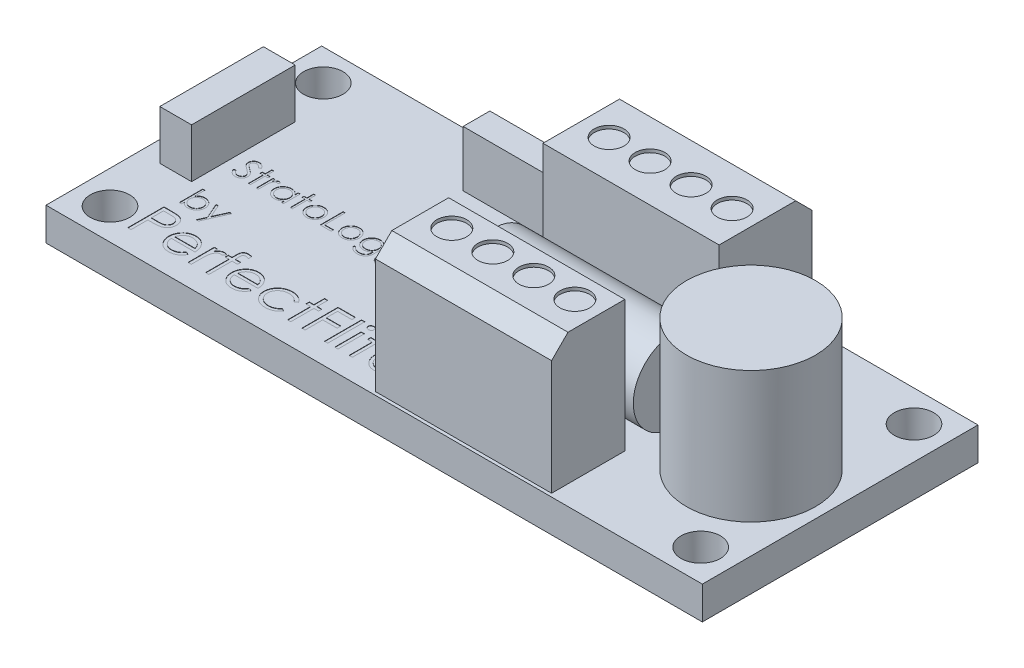
SolidWorks part; units mm, degrees
ref_plane "Front Plane" through (0, 0, 0) normal (0, 0, 1) x (1, 0, 0)
ref_plane "Top Plane" through (0, 0, 0) normal (0, 1, 0) x (1, 0, 0)
ref_plane "Right Plane" through (0, 0, 0) normal (1, 0, 0) x (0, 0, -1)
sketch "Sketch1" plane through (0, 0, 0) normal (0, 1, 0) x (1, 0, 0)
  line L1 (-19.9595, 12.6467) -> (30.8405, 12.6467)
  line L2 (-19.9595, 12.6467) -> (-19.9595, -8.6893)
  line L3 (-19.9595, -8.6893) -> (30.8405, -8.6893)
  line L4 (30.8405, 12.6467) -> (30.8405, -8.6893)
  dimension "D1" = 21.336
  dimension "D2" = 50.8
extrude "Boss-Extrude1" add sketch "Sketch1" along normal blind 1.27
sketch "Sketch2" plane through (0, 1.27, 0) normal (0, 1, 0) x (1, 0, 0)
  line L0 (-19.9595, 12.6467) -> (-19.9595, -8.6893) construction
  line L1 (30.8405, -8.6893) -> (30.8405, 12.6467) construction
  line L2 (-19.9595, -8.6893) -> (30.8405, -8.6893) construction
  circle A0 centre (-17.4195, 10.2337) radius 1.524
  circle A1 centre (28.3005, 10.2337) radius 1.524
  circle A2 centre (28.3005, -6.2763) radius 1.524
  circle A3 centre (-17.4195, -6.2763) radius 1.524
  dimension "D1" = 3.048
  dimension "D2" = 3.048
  dimension "D3" = 3.048
  dimension "D4" = 3.048
  dimension "D5" = 45.72
  dimension "D6" = 45.72
  dimension "D7" = 16.51
  dimension "D8" = 16.51
  dimension "D9" = 2.54
  dimension "D10" = 2.54
  dimension "D11" = 2.413
extrude "Cut-Extrude1" cut sketch "Sketch2" against normal blind 1.27
sketch "Sketch3" plane through (0, 1.27, 0) normal (0, 1, 0) x (1, 0, 0)
  line L0 (-330.3403, 62.2564) -> (-39.6736, 62.2564) construction
  line L1 (-19.9595, -8.6893) -> (30.8405, -8.6893) construction
  line L2 (5.2838, 11.7263) -> (18.9186, 11.7263)
  line L3 (5.2838, 11.7263) -> (5.2838, 4.5331)
  line L4 (5.2838, 4.5331) -> (18.9186, 4.5331)
  line L5 (18.9186, 11.7263) -> (18.9186, 4.5331)
  line L6 (5.2838, -2.7674) -> (18.9186, -2.7674)
  line L7 (5.2838, -2.7674) -> (5.2838, -8.6893)
  line L8 (5.2838, -8.6893) -> (18.9186, -8.6893)
  line L9 (18.9186, -2.7674) -> (18.9186, -8.6893)
  circle A0 centre (25.0381, 0.8829) radius 4.9954
extrude "Boss-Extrude2" add sketch "Sketch3" along normal blind 11.43
sketch "Sketch6" plane through (0, 0, 0) normal (0, -1, 0) x (1, 0, 0)
  line L4 (-19.9595, 8.6893) -> (-19.9595, -12.6467)
  line L5 (-19.9595, -12.6467) -> (30.8405, -12.6467)
  line L6 (30.8405, -12.6467) -> (30.8405, 8.6893)
  line L7 (30.8405, 8.6893) -> (-19.9595, 8.6893)
  line L8 (-19.9595, 8.6893) -> (-19.9595, -12.6467)
  line L9 (-19.9595, -12.6467) -> (30.8405, -12.6467)
  line L10 (30.8405, -12.6467) -> (30.8405, 8.6893)
  line L11 (30.8405, 8.6893) -> (-19.9595, 8.6893)
  dimension "D1" = 0
extrude "Boss-Extrude3" add sketch "Sketch6" against normal blind 2.54
extrude "Cut-Extrude4" cut sketch "Sketch2<5>" against normal through all both and the other way through all contours A1
sketch "Sketch2<5>" plane through (0, 1.27, 0) normal (0, 1, 0) x (1, 0, 0) same geometry as "Sketch2"
extrude "Cut-Extrude5" cut sketch "Sketch2<7>" against normal through all both and the other way through all contours A2 | A3 | A0
sketch "Sketch2<7>" plane through (0, 1.27, 0) normal (0, 1, 0) x (1, 0, 0) same geometry as "Sketch2"
sketch "Sketch11" plane through (0, 0, 8.6893) normal (0, 0, 1) x (1, 0, 0)
  line L1 (18.9186, 12.7) -> (5.2838, 12.7)
  line L2 (18.9186, 12.7) -> (18.9186, 2.54)
  line L3 (18.9186, 2.54) -> (5.2838, 2.54)
  line L4 (5.2838, 12.7) -> (5.2838, 2.54)
extrude "Cut-Extrude6" cut sketch "Sketch11" against normal blind 0.254
chamfer "Chamfer2" distance 1.27 angle 45 2 edges at (12.1012, 12.7, 8.4353) (12.1012, 12.7, -11.7263)
sketch "Sketch12" plane through (0, 2.54, 0) normal (0, 1, 0) x (1, 0, 0)
  line L1 (-18.3583, 6.538) -> (-15.9008, 6.538)
  line L2 (-18.3583, 6.538) -> (-18.3583, -1.4811)
  line L3 (-18.3583, -1.4811) -> (-15.9008, -1.4811)
  line L4 (-15.9008, 6.538) -> (-15.9008, -1.4811)
extrude "Boss-Extrude4" add sketch "Sketch12" along normal blind 3.81
ref_plane "Plane1" through (5.08, 0, 0) normal (1, 0, 0) x (0, 0, -1)
sketch "Sketch15" plane through (5.08, 0, 0) normal (1, 0, 0) x (0, 0, -1)
  circle A0 centre (0.933, 5.5284) radius 3.175
extrude "Boss-Extrude5" add sketch "Sketch15" along normal blind 13.97
sketch "Sketch16" plane through (0, 2.54, 0) normal (0, 1, 0) x (1, 0, 0)
  line L1 (-4.7774, 10.4829) -> (1.8836, 10.4829)
  line L2 (-4.7774, 10.4829) -> (-4.7774, 8.4135)
  line L3 (-4.7774, 8.4135) -> (1.8836, 8.4135)
  line L4 (1.8836, 10.4829) -> (1.8836, 8.4135)
extrude "Boss-Extrude6" add sketch "Sketch16" along normal blind 4.318
sketch "Sketch17" plane through (0, 12.7, 0) normal (0, 1, 0) x (1, 0, 0)
  line L4 (5.2838, -2.7674) -> (5.2838, -7.1653)
  line L5 (5.2838, -7.1653) -> (18.9186, -7.1653)
  line L6 (18.9186, -7.1653) -> (18.9186, -2.7674)
  line L7 (18.9186, -2.7674) -> (5.2838, -2.7674)
  line L8 (5.2838, -2.7674) -> (5.2838, -7.1653)
  line L9 (5.2838, -7.1653) -> (18.9186, -7.1653)
  line L10 (18.9186, -7.1653) -> (18.9186, -2.7674)
  line L11 (18.9186, -2.7674) -> (5.2838, -2.7674)
  circle A0 centre (7.4493, 7.4817) radius 1.1514
  circle A1 centre (10.6243, 7.4817) radius 1.1514
  circle A2 centre (13.7993, 7.4817) radius 1.1514
  circle A3 centre (16.9743, 7.4817) radius 1.1514
  circle A4 centre (7.4493, -4.6909) radius 1.1514
  circle A5 centre (10.6243, -4.6909) radius 1.1514
  circle A6 centre (13.7993, -4.6909) radius 1.1514
  circle A7 centre (16.9743, -4.6909) radius 1.1514
  dimension "D2" = 3.175
  dimension "D3" = 3.175
  dimension "D4" = 3.175
  dimension "D5" = 3.175
  dimension "D6" = 3.175
  dimension "D7" = 3.175
  dimension "D1" = 0
extrude "Cut-Extrude7" cut sketch "Sketch17" against normal blind 0.254 contours A0 | A1 | A2 | A3 | A5 | A4 | A7 | A6
sketch "Sketch19" plane through (0, 2.54, 0) normal (0, 1, 0) x (1, 0, 0)
  text T0 "StratoLoggerCF\r\nby" font "Century Gothic" height 1.778
  text T1 "PerfectFlite" font "Century Gothic" height 2.794
extrude "Cut-Extrude8" cut sketch "Sketch19" against normal blind 0.0254
